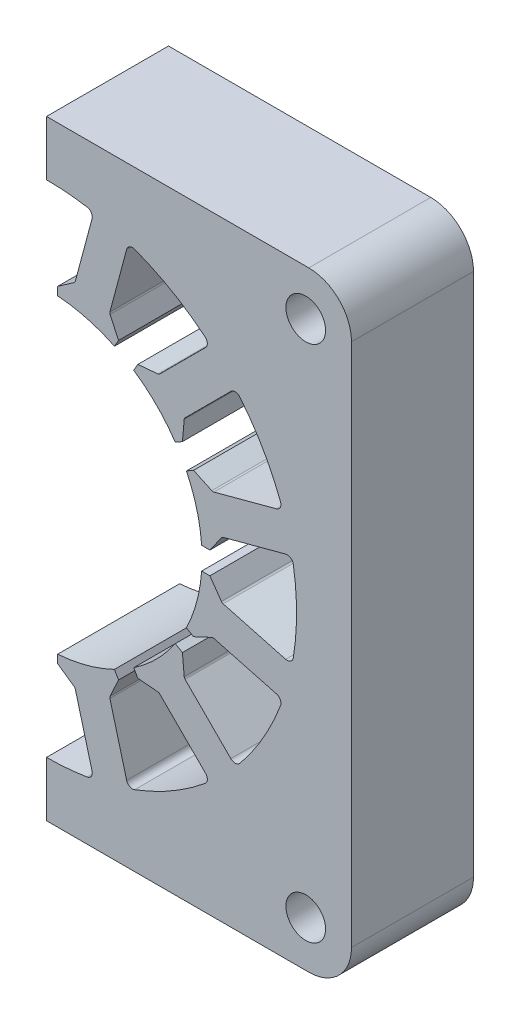
SolidWorks part; units mm, degrees
ref_plane "Front" through (0, 0, 0) normal (0, 0, 1) x (1, 0, 0)
ref_plane "Top" through (0, 0, 0) normal (0, 1, 0) x (1, 0, 0)
ref_plane "Right" through (0, 0, 0) normal (1, 0, 0) x (0, 0, -1)
sketch "Sketch1" plane through (0, 0, 0) normal (0, 0, 1) x (1, 0, 0)
  line L1 (-50, 50) -> (50, 50)
  line L2 (-50, 50) -> (-50, -50)
  line L3 (-50, -50) -> (50, -50)
  line L4 (50, 50) -> (50, -50)
  circle A0 centre (0, 0) radius 50 construction
  circle A1 centre (0, 0) radius 25.5
  dimension "D1" = 100
  dimension "D2" = 51
extrude "Lamination Extruction" add sketch "Sketch1" along normal blind 20
ref_axis "Axis1" through (0, 0, 20) along (0, 0, -1)
sketch "Sketch2" plane through (0, 0, 20) normal (0, 0, 1) x (1, 0, 0)
  line L0 (0, 0) -> (0, 50) construction
  line L1 (50, 50) -> (-50, 50) construction
  line L2 (-1.825, 26.7846) -> (1.825, 26.7846) construction
  line L3 (7.75, 40.2609) -> (4.6735, 28.7791)
  line L4 (4.6735, 28.7791) -> (1.825, 26.7846)
  line L5 (-1.825, 26.7846) -> (-1.825, 25.4346)
  line L6 (-7.75, 40.2609) -> (-4.6735, 28.7791)
  line L7 (-4.6735, 28.7791) -> (-1.825, 26.7846)
  line L8 (1.825, 26.7846) -> (1.825, 25.4346)
  line L9 (-4.6735, 28.7791) -> (4.6735, 28.7791) construction
  arc A1 (-7.75, 40.2609) -> (7.75, 40.2609) centre (0, 0) cw
  circle A3 centre (0, 0) radius 25.5 construction
  arc A4 (1.825, 25.4346) -> (-1.825, 25.4346) centre (0, 0) ccw
  point P7 (0, 26.7846)
  point P16 (0, 41)
  point P19 (0, 28.7791)
  circle M15 centre (0, 0) radius 25.5
  dimension "D2" = 41
  dimension "D1" = 30
  dimension "D3" = 15.5
  dimension "D6" = 35
  dimension "D4" = 1.35
  dimension "D5" = 3.65
extrude "Slot Cut" cut sketch "Sketch2" against normal through all contours A1 L6 L7 L5 L8 L4 L3 M15 region at (0, 34.4506, 20)
fillet "Slot Fillet Top" radius 1 2 edges at (7.75, 40.2609, 10) (-7.75, 40.2609, 10)
fillet "Slot Fillet Bottom" radius 0.5 2 edges at (4.6735, 28.7791, 10) (-4.6735, 28.7791, 10)
pattern_circular "Slot Duplicate" count 12 over 360 about axis through (0, 0, 20) along (0, 0, -1) of "Slot Cut", "Slot Fillet Top", "Slot Fillet Bottom"
sketch "Sketch3" plane through (0, 0, 20) normal (0, 0, 1) x (1, 0, 0)
  line L1 (42.5, 42.5) -> (-42.5, 42.5) construction
  line L2 (42.5, 42.5) -> (42.5, -42.5) construction
  line L3 (42.5, -42.5) -> (-42.5, -42.5) construction
  line L4 (-42.5, 42.5) -> (-42.5, -42.5) construction
  line L5 (42.5, 42.5) -> (-42.5, -42.5) construction
  line L6 (42.5, -42.5) -> (-42.5, 42.5) construction
  circle A1 centre (-42.5, 42.5) radius 3.25
  circle A2 centre (42.5, 42.5) radius 3.25
  circle A3 centre (42.5, -42.5) radius 3.25
  circle A4 centre (-42.5, -42.5) radius 3.25
  point P0 (0, 0)
  dimension "D2" = 6.5
  dimension "D1" = 85
extrude "Bolt Hole Cut" cut sketch "Sketch3" against normal through all
fillet "Corner Fillet" radius 7 4 edges at (-50, 50, 10) (-50, -50, 10) (50, -50, 10) (50, 50, 10)
sketch "Sketch4" plane through (0, 0, 20) normal (0, 0, 1) x (1, 0, 0)
  line L0 (-50, 43) -> (-50, -43) construction
  line L1 (-50, -50) -> (0, -50)
  line L2 (-50, -50) -> (-50, 50)
  line L3 (-50, 50) -> (0, 50)
  line L4 (0, -50) -> (0, 50)
  line L6 (43, 50) -> (-43, 50) construction
  line L7 (-43, -50) -> (43, -50) construction
extrude "Cut-Extrude1" cut sketch "Sketch4" against normal through all
equation "\"DS1\"= 100mm"
equation "\"D1@Sketch1\"=\"DS1\""
equation "\"DS2\"=51"
equation "\"D2@Sketch1\"=\"DS2\""
equation "\"HEIGHT\"=20"
equation "\"D1@Lamination Extruction\" = \"HEIGHT\""
equation "\"AngSlot\"=30"
equation "\"D1@Sketch2\"=\"AngSlot\""
equation "\"DSS\"= 15.5mm"
equation "\"D2@Sketch2\"=\"DSS\"+\"DS2\"/2"
equation "\"WSSB\"=15.5"
equation "\"D3@Sketch2\"=\"WSSB\""
equation "\"WSSO\"=3.65"
equation "\"HSTT\"=1.35"
equation "\"AngSTT\"=35"
equation "\"D6@Sketch2\"=\"AngSTT\""
equation "\"D4@Sketch2\"=\"HSTT\""
equation "\"D5@Sketch2\"=\"WSSO\""
equation "\"FRSSB\"=1"
equation "\"D1@Slot Fillet Top\" = \"FRSSB\""
equation "\"FRSST\"=0.5"
equation "\"D1@Slot Fillet Bottom\" = \"FRSST\""
equation "\"SLOTS\"=12"
equation "\"D1@Slot Duplicate\" = \"SLOTS\""
equation "\"HOLE_BOLT\"= 85"
equation "\"D1@Sketch3\"=\"HOLE_BOLT\""
equation "\"BOLT_DIA\"=6.5"
equation "\"D2@Sketch3\"=\"BOLT_DIA\""
equation "\"LAM_FILLET\"=7"
equation "\"D1@Corner Fillet\"=\"LAM_FILLET\""
